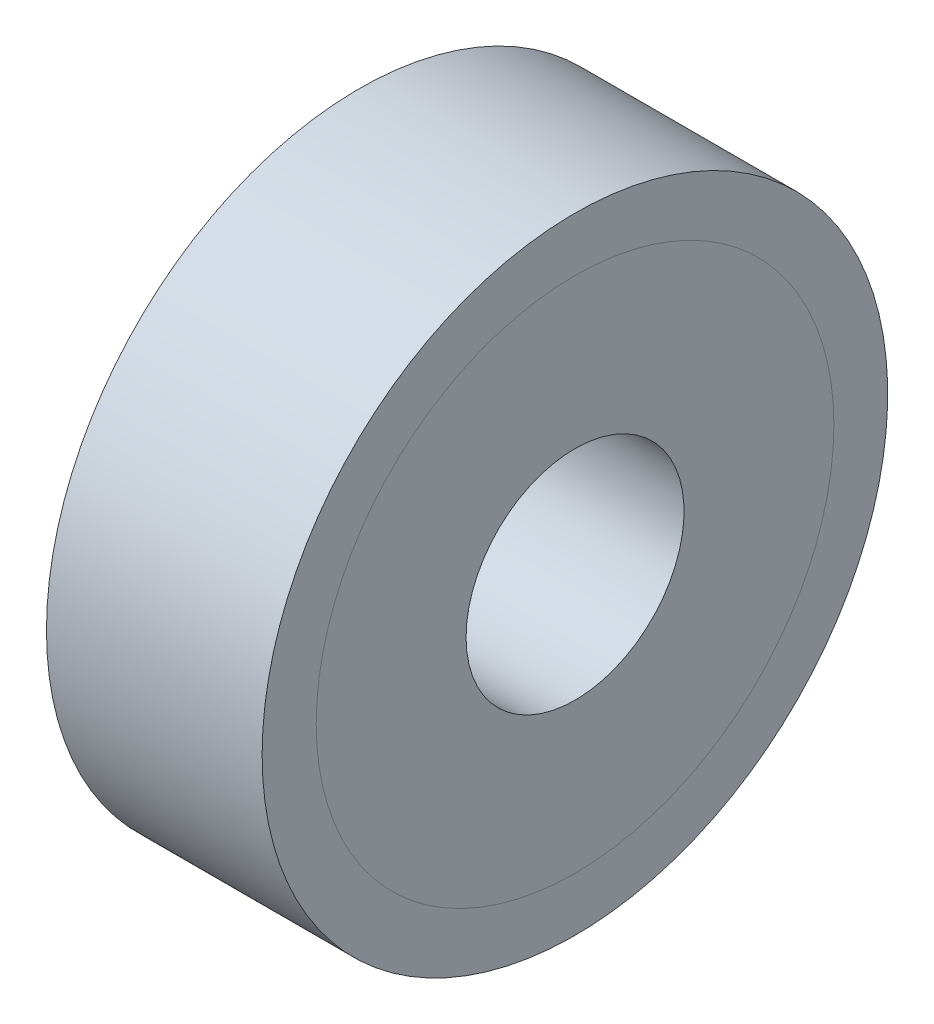
SolidWorks part; units mm, degrees
ref_plane "Front Plane" through (0, 0, 0) normal (0, 0, 1) x (1, 0, 0)
ref_plane "Top Plane" through (0, 0, 0) normal (0, 1, 0) x (1, 0, 0)
ref_plane "Right Plane" through (0, 0, 0) normal (1, 0, 0) x (0, 0, -1)
sketch "Sketch1" plane through (0, 0, 0) normal (0, 1, 0) x (1, 0, 0)
  line L1 (0, 0) -> (15.88, 0) construction
  line L2 (0, 0) -> (0, 19.05) construction
  line L4 (15.88, 0) -> (15.88, 19.05) construction
  line L5 (7.94, 0) -> (7.94, 32.3839) construction
  line L6 (11.91, 23.02) -> (15.8712, 23.02)
  line L7 (15.8712, 23.02) -> (15.88, 19.05)
  line L9 (0, 6.329) -> (0, 8.02)
  line L10 (0, 9.525) -> (0, 10.2981)
  line L11 (15.88, 8.02) -> (0, 8.02)
  line L12 (15.88, 9.525) -> (15.88, 19.05)
  line L13 (0, 8.02) -> (0, 19.05)
  line L14 (15.88, 8.02) -> (15.88, 19.05)
  line L15 (15.88, 19.05) -> (15.8712, 19.2247)
  line L16 (3.97, 23.02) -> (11.91, 23.02)
  line L17 (0, 19.05) -> (0, 23.02)
  line L18 (0, 23.02) -> (3.97, 23.02)
  dimension "D1" = 15
  dimension "D4" = 15.88
revolve "Revolve1" add sketch "Sketch1" angle 360 about L1 region at (7.9394, 0, -15.5195)
sketch3d "3DSketch1" plane through (0, 0, 0) normal (0, 0, 1) x (1, 0, 0)
  dimension "D1" = 10
sketch "Sketch3" plane through (15.88, 0, 0) normal (1, 0, 0) x (0, 0, -1)
  circle A0 centre (0, 0) radius 10
  dimension "D1" = 20
